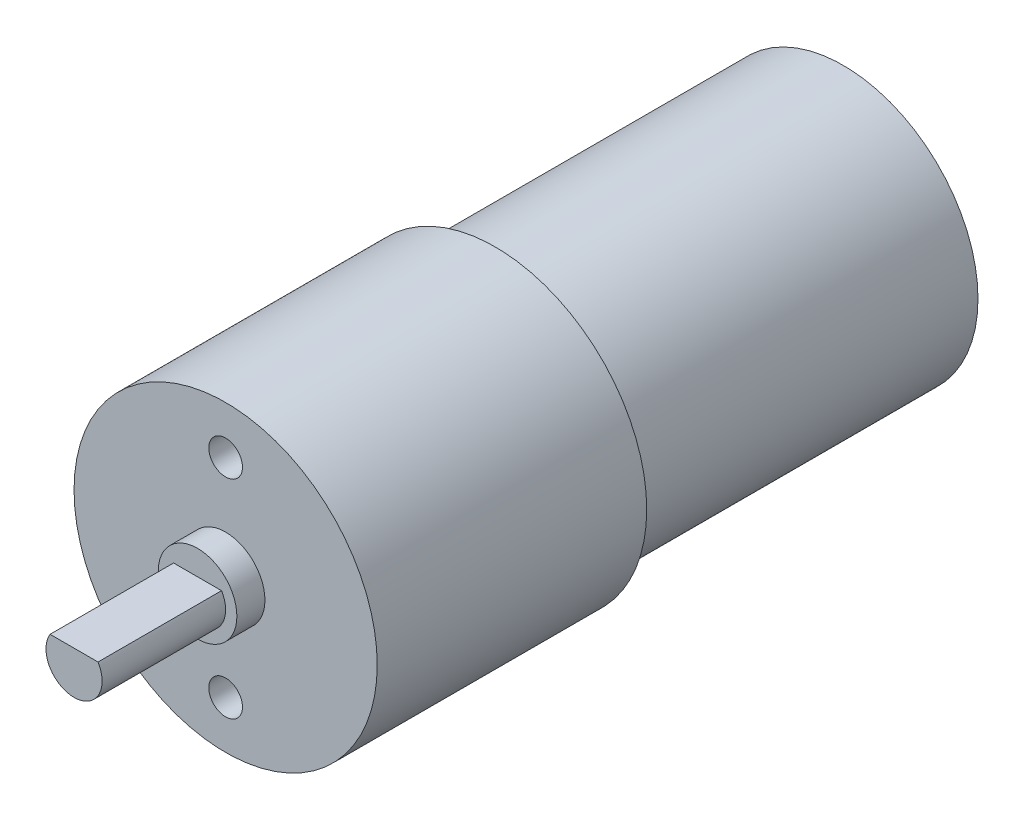
SolidWorks part; units mm, degrees
ref_plane "Front Plane" through (0, 0, 0) normal (0, 0, 1) x (1, 0, 0)
ref_plane "Top Plane" through (0, 0, 0) normal (0, 1, 0) x (1, 0, 0)
ref_plane "Right Plane" through (0, 0, 0) normal (1, 0, 0) x (0, 0, -1)
sketch "Sketch1" plane through (0, 0, 0) normal (0, 0, 1) x (1, 0, 0)
  circle A0 centre (0, 0) radius 13.5
  circle A1 centre (0, 0) radius 12
  dimension "D1" = 27
  dimension "D2" = 24
extrude "Boss-Extrude1" add sketch "Sketch1" against normal blind 24 contours A0
extrude "Boss-Extrude2" add sketch "Sketch1<3>" against normal blind 31 from surface contours A1 region at (0, 0, 0) starting at face at (13.5, 0, -24)
sketch "Sketch1<3>" plane through (0, 0, 0) normal (0, 0, 1) x (1, 0, 0) same geometry as "Sketch1"
sketch "Sketch2" plane through (0, 0, 0) normal (0, 0, 1) x (1, 0, 0)
  line L0 (-2.1354, 1.3) -> (2.1354, 1.3)
  line L1 (-2.4495, -2.5) -> (2.4495, -2.5) construction
  circle A0 centre (0, 0) radius 3.5
  circle A1 centre (0, 0) radius 2.5
  dimension "D1" = 7
  dimension "D2" = 5
  dimension "D3" = 3.8
extrude "Boss-Extrude3" add sketch "Sketch2" along normal blind 2.5 contours A0
extrude "Boss-Extrude4" add sketch "Sketch2<3>" along normal blind 11 from surface contours L0 A1 region at (0, -0.4054, 0) starting at face at (3.5, 0, 2.5)
sketch "Sketch2<3>" plane through (0, 0, 0) normal (0, 0, 1) x (1, 0, 0) same geometry as "Sketch2"
sketch "Sketch3" plane through (0, 0, 0) normal (0, 0, 1) x (1, 0, 0)
  circle A0 centre (0, 0) radius 7.75 construction
  circle A1 centre (0, 9.25) radius 1.5
  circle A2 centre (0, -9.25) radius 1.5
  dimension "D1" = 15.5
  dimension "D2" = 3
extrude "Cut-Extrude1" cut sketch "Sketch3" against normal blind 4
